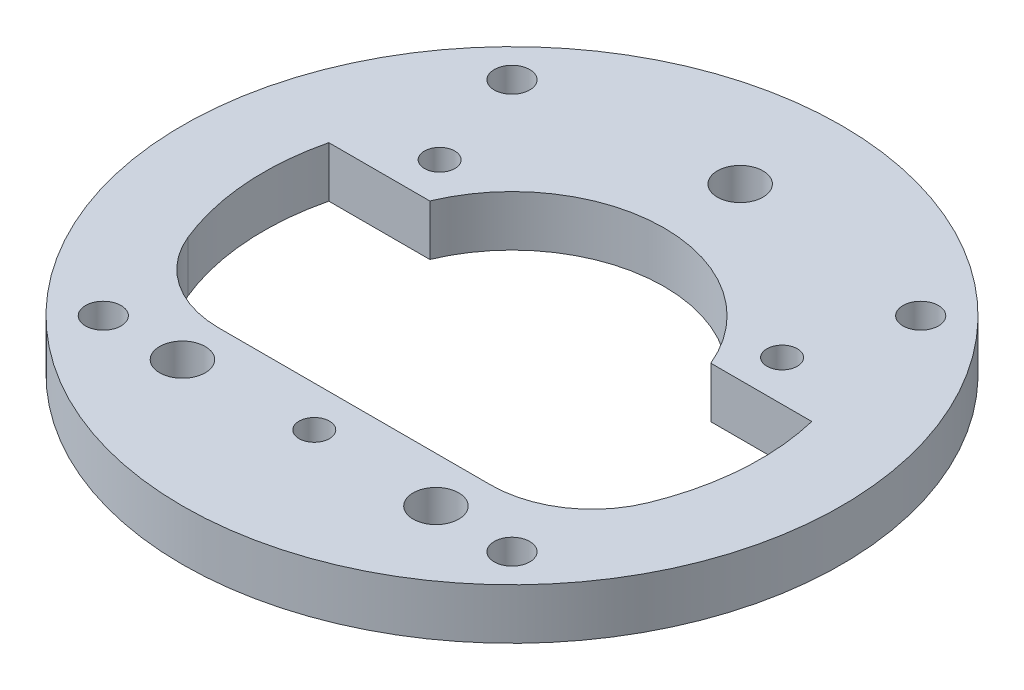
SolidWorks part; units mm, degrees
ref_plane "Front Plane" through (0, 0, 0) normal (0, 0, 1) x (1, 0, 0)
ref_plane "Top Plane" through (0, 0, 0) normal (0, 1, 0) x (1, 0, 0)
ref_plane "Right Plane" through (0, 0, 0) normal (1, 0, 0) x (0, 0, -1)
sketch "Sketch1" plane through (0, 0, 0) normal (0, 1, 0) x (1, 0, 0)
  circle A0 centre (0, 0) radius 32.5
  circle A1 centre (0, 0) radius 24.5
  dimension "D1" = 65
  dimension "D2" = 8
extrude "Boss-Extrude1" add sketch "Sketch1" along normal blind 5
sketch "Sketch2" plane through (0, 5, 0) normal (0, 1, 0) x (1, 0, 0)
  line L0 (-18.9737, -15.5) -> (18.9737, -15.5)
  line L1 (-23.8157, 5.75) -> (-13.8542, 5.75)
  line L2 (0, 0) -> (7.7557, 0) construction
  line L3 (13.8542, 5.75) -> (23.8157, 5.75)
  line L4 (-20.1525, 20.1525) -> (0, 0) construction
  circle A0 centre (0, 22.5) radius 2.25 construction
  circle A1 centre (-12.5, -20) radius 2.25 construction
  circle A2 centre (12.5, -20) radius 2.25 construction
  circle A3 centre (0, -19.5) radius 1.5 construction
  circle A4 centre (0, 0) radius 19.5 construction
  circle A5 centre (-16.8875, 9.75) radius 1.5 construction
  circle A6 centre (0, 0) radius 24.5 construction
  circle A7 centre (16.8875, 9.75) radius 1.5 construction
  arc A8 (-13.8542, 5.75) -> (13.8542, 5.75) centre (0, 0) cw
  arc A9 (-1.0754, 24.4764) -> (-14.7125, -19.5907) centre (0, 0) ccw
  arc A10 (14.7125, -19.5907) -> (1.0754, 24.4764) centre (0, 0) ccw
  arc A11 (-11.1625, -21.8093) -> (11.1625, -21.8093) centre (0, 0) ccw
  circle A12 centre (0, 0) radius 28.5 construction
  circle A13 centre (0, 0) radius 32.5 construction
  circle A14 centre (-20.1525, 20.1525) radius 1.75 construction
  circle A15 centre (20.1525, 20.1525) radius 1.75 construction
  circle A16 centre (20.1525, -20.1525) radius 1.75 construction
  circle A17 centre (-20.1525, -20.1525) radius 1.75 construction
  point P19 (0, 0)
  point P44 (0, 0)
  circle M2 centre (0, 0) radius 24.5
  dimension "D5" = 4.5
  dimension "D6" = 4.5
  dimension "D7" = 4.5
  dimension "D10" = 3
  dimension "D12" = 15
  dimension "D16" = 3.5
  dimension "D1" = 25
  dimension "D2" = 12.5
  dimension "D3" = 22.5
  dimension "D4" = 20
  dimension "D9" = 5
  dimension "D11" = 4
  dimension "D13" = 4
  dimension "D14" = 4
  dimension "D15" = 135
  dimension "D8" = 3
  dimension "D17" = 4
extrude "Saliente-Extruir1" add sketch "Sketch2" against normal up to surface (5 mm away) contours L1 A8 L3 A0 A7 A5 M2 | A2 L0 A1 A3 M2 region at (0, 5, 19.1635) region at (0, 5, -15.1158) up to face at (0, 0, 32.5)
sketch "Croquis1" plane through (0, 5, 0) normal (0, 1, 0) x (1, 0, 0)
  circle A0 centre (-20.1525, 20.1525) radius 1.75 construction
  circle A1 centre (-20.1525, 20.1525) radius 1.75
  circle A2 centre (0, 22.5) radius 2.25 construction
  circle A3 centre (0, 22.5) radius 2.25
  circle A4 centre (20.1525, 20.1525) radius 1.75 construction
  circle A5 centre (20.1525, 20.1525) radius 1.75
  circle A6 centre (-16.8875, 9.75) radius 1.5 construction
  circle A7 centre (-16.8875, 9.75) radius 1.5
  circle A8 centre (16.8875, 9.75) radius 1.5 construction
  circle A9 centre (16.8875, 9.75) radius 1.5
  circle A10 centre (0, -19.5) radius 1.5 construction
  circle A11 centre (0, -19.5) radius 1.5
  circle A12 centre (12.5, -20) radius 2.25 construction
  circle A13 centre (12.5, -20) radius 2.25
  circle A14 centre (-12.5, -20) radius 2.25 construction
  circle A15 centre (-12.5, -20) radius 2.25
  circle A16 centre (-20.1525, -20.1525) radius 1.75 construction
  circle A17 centre (-20.1525, -20.1525) radius 1.75
  circle A18 centre (20.1525, -20.1525) radius 1.75 construction
  circle A19 centre (20.1525, -20.1525) radius 1.75
extrude "Cortar-Extruir1" cut sketch "Croquis1" against normal up to next
fillet "Redondeo1" radius 10 2 edges at (18.9737, 2.5, 15.5) (-18.9737, 2.5, 15.5)
equation "\"D2@Sketch2\"=\"D1@Sketch2\"/2"
equation "\"D6@Sketch2\"=\"D5@Sketch2\""
equation "\"D7@Sketch2\"=\"D6@Sketch2\""
equation "\"D10@Sketch2\"=\"D8@Sketch2\""
